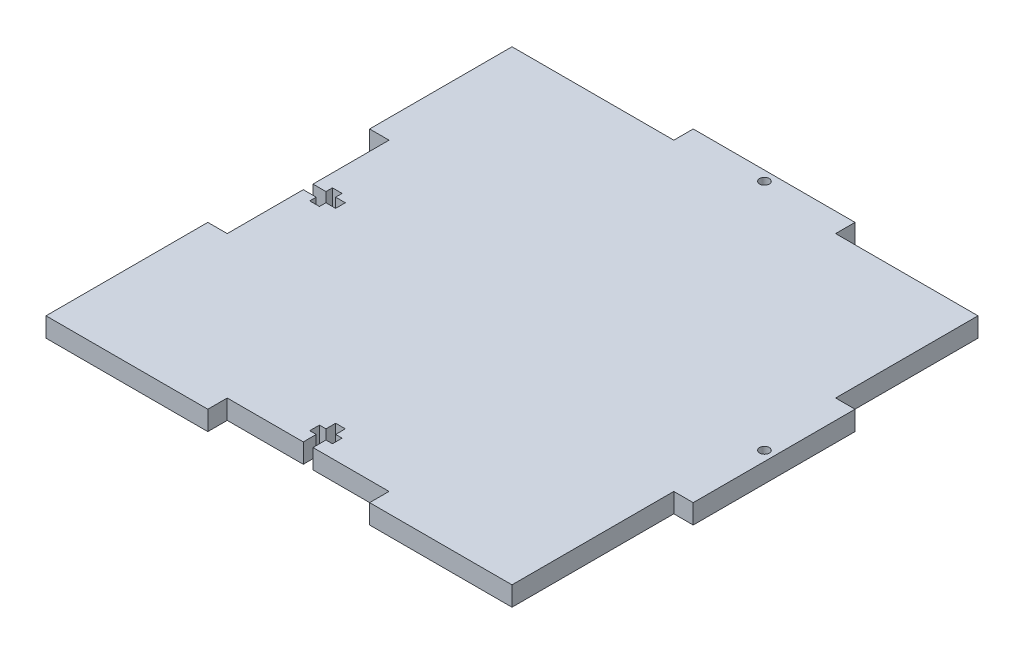
SolidWorks part; units mm, degrees
material "Acrylic (Medium-high impact)"
ref_plane "Front Plane" through (0, 0, 0) normal (0, 0, 1) x (1, 0, 0)
ref_plane "Top Plane" through (0, 0, 0) normal (0, 1, 0) x (1, 0, 0)
ref_plane "Right Plane" through (0, 0, 0) normal (1, 0, 0) x (0, 0, -1)
sketch "Sketch1" plane through (0, 0, 0) normal (0, 1, 0) x (1, 0, 0)
  line L0 (-72, 28) -> (-66, 28)
  line L1 (-72, -72) -> (72, -72)
  line L2 (-72, -72) -> (-72, 72)
  line L3 (-72, 72) -> (72, 72)
  line L4 (72, -72) -> (72, 72)
  line L5 (-72, -72) -> (72, 72) construction
  line L6 (-72, 72) -> (72, -72) construction
  line L7 (-66, 28) -> (-66, -22)
  line L8 (28, -72) -> (28, -66)
  line L9 (-22, 72) -> (-22, 78)
  line L10 (-22, 78) -> (28, 78)
  line L11 (28, 72) -> (28, 78)
  line L12 (72, 28) -> (78, 28)
  line L13 (78, 28) -> (78, -22)
  line L14 (-22, -72) -> (-22, -66)
  line L15 (-22, -66) -> (28, -66)
  line L16 (3, 78) -> (3, -72) construction
  line L17 (-72, 3) -> (78, 3) construction
  line L18 (72, -22) -> (78, -22)
  line L19 (-72, -22) -> (-66, -22)
  line L20 (75, 28) -> (75, -22) construction
  line L21 (4.5, -66) -> (4.5, -62)
  line L22 (4.5, -62) -> (6.5, -62)
  line L23 (6.5, -62) -> (6.5, -59)
  line L24 (6.5, -59) -> (4.5, -59)
  line L25 (4.5, -59) -> (4.5, -56)
  line L26 (4.5, -56) -> (1.5, -56)
  line L27 (1.5, -66) -> (1.5, -62)
  line L28 (1.5, -62) -> (-0.5, -62)
  line L29 (-0.5, -59) -> (1.5, -59)
  line L30 (-0.5, -62) -> (-0.5, -59)
  line L31 (1.5, -59) -> (1.5, -56)
  line L32 (-59, 4.5) -> (-56, 4.5)
  line L33 (-62, 4.5) -> (-62, 6.5)
  line L34 (-59, 6.5) -> (-59, 4.5)
  line L35 (-62, 6.5) -> (-59, 6.5)
  line L36 (-66, 4.5) -> (-62, 4.5)
  line L37 (-66, 1.5) -> (-62, 1.5)
  line L38 (-62, 1.5) -> (-62, -0.5)
  line L39 (-62, -0.5) -> (-59, -0.5)
  line L40 (-59, -0.5) -> (-59, 1.5)
  line L41 (-59, 1.5) -> (-56, 1.5)
  line L42 (-56, 4.5) -> (-56, 1.5)
  circle A0 centre (75, 3) radius 1.5
  circle A1 centre (3, 75) radius 1.5
  point P0 (0, 0)
  point P22 (3, 3)
  point P27 (3, 3)
  point P40 (3, -66)
  point P45 (-66, 3)
  point P49 (3, -56)
  point P61 (4.5, -59)
  point P62 (4.5, -59)
  dimension "D4" = 3
  dimension "D1" = 144
  dimension "D2" = 25
  dimension "D3" = 6
  dimension "D5" = 4
  dimension "D6" = 2
  dimension "D7" = 3
  dimension "D8" = 1.5
extrude "Boss-Extrude1" add sketch "Sketch1" along normal blind 6 contours L19 L2 L1 L14 L15 L8 L4 L3 L0 L7 | L3 L11 L10 L9 | L4 L18 L13 L12 region at (1.1086, 0, -1.1086) region at (-21.4964, 0, -75) region at (75, 0, -27.4964)
